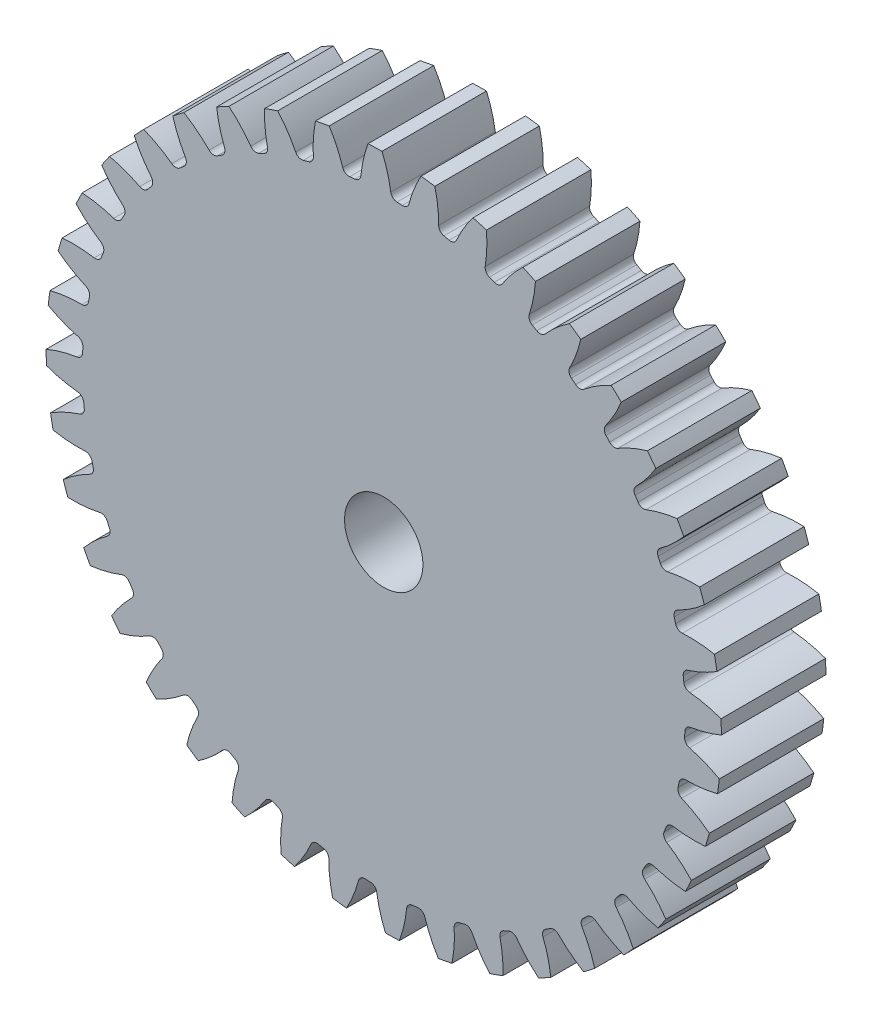
SolidWorks part; units mm, degrees
ref_plane "Front" through (0, 0, 0) normal (0, 0, 1) x (1, 0, 0)
ref_plane "Top" through (0, 0, 0) normal (0, 1, 0) x (1, 0, 0)
ref_plane "Right" through (0, 0, 0) normal (1, 0, 0) x (0, 0, -1)
sketch "Sketch3" plane through (0, 0, 0) normal (0, 0, 1) x (1, 0, 0)
  circle A0 centre (0, 0) radius 20.5154
  dimension "od" = 41.0308
extrude "gearBody" add sketch "Sketch3" along normal blind 6.35
sketch "Sketch2" plane through (0, 0, 0) normal (0, 0, 1) x (1, 0, 0)
  line L0 (0, 0) -> (17.4762, 7.2389) construction
  line L1 (23.4466, -5.3664) -> (0, 0) construction
  line L2 (0, 0) -> (36.3143, 0) construction
  line L3 (19.537, -0.2349) -> (19.4534, -1.8214) construction
  line L5 (19.4952, -1.0281) -> (0, 0) construction
  line L7 (0, 0) -> (18.9161, 0) construction
  arc A0 (18.9123, -0.3796) -> (18.8473, -1.6117) centre (0, 0) ccw construction
  arc A1 (20.5151, 0.1066) -> (20.3901, -2.2639) centre (0, 0) ccw construction
  arc A2 (19.537, -0.2349) -> (19.4534, -1.8214) centre (0, 0) ccw construction
  arc A3 (18.2806, -1.1275) -> (18.2978, -0.8016) centre (0, 0) ccw
  arc A4 (23.4466, -5.3664) -> (18.5763, -1.5357) centre (16.6179, -9.0369) ccw
  arc A5 (23.4466, -5.3664) -> (23.881, 2.8705) centre (0, 0) ccw
  arc A6 (23.881, 2.8705) -> (18.6348, -0.4267) centre (17.4762, 7.2389) cw
  arc A7 (18.2978, -0.8016) -> (18.6348, -0.4267) centre (18.6941, -0.8189) cw
  arc A8 (18.5763, -1.5357) -> (18.2806, -1.1275) centre (18.6765, -1.1519) cw
  point P6 (23.881, 2.8705)
  point P22 (23.4466, -5.3664)
  dimension "baseDia" = 37.8322
  dimension "od" = 41.0308
  dimension "pd" = 39.0769
  dimension "rd" = 36.6307
  dimension "rFillet" = 0.3966
  dimension "pointX" = 23.881
  dimension "pointY" = 2.8705
  dimension "CTT" = 1.5865
  dimension "flankCenterAngle" = 22.5
extrude "toothCut" cut sketch "Sketch2" along normal through all
pattern_circular "CirPattern1" count 40 over 360 about axis through (0, 0, 6.35) along (0, 0, -1) of "toothCut"
ref_axis "toothSpace" through (0, 0, 0) along (0.9986, -0.0527, 0)
ref_axis "Axis2" through (20.339, -2.6845, 0) along (-0.9914, 0.1309, 0)
sketch "hub1Dia" plane through (0, 0, 0) normal (0, 0, -1) x (-1, 0, 0)
  circle A0 centre (0, 0) radius 12.7
  dimension "hub1Dia" = 25.4
sketch "hub2Dia" plane through (0, 0, 6.35) normal (0, 0, 1) x (1, 0, 0)
  circle A0 centre (0, 0) radius 12.7
  dimension "hub2dia" = 25.4
sketch "boreDia" plane through (0, 0, 0) normal (0, 0, 1) x (1, 0, 0)
  circle A0 centre (0, 0) radius 2.3812
  dimension "boreDia" = 4.7625
extrude "bore" cut sketch "boreDia" against normal mid plane 25400
sketch "kwy1sketch" plane through (0, 0, 0) normal (0, 0, 1) x (1, 0, 0)
  line L0 (-6.0395, 0.6368) -> (0, 0) construction
  line L1 (28.9598, 9.717) -> (26.2964, -15.543)
  line L2 (26.2964, -15.543) -> (-5.2785, -12.2138)
  line L3 (28.9598, 9.717) -> (-2.6152, 13.0461)
  line L4 (-5.2785, -12.2138) -> (0, 0)
  line L5 (0, 0) -> (-2.6152, 13.0461)
  line L6 (0, 0) -> (18.2899, -0.9646) construction
  line L7 (27.6281, -2.913) -> (0, 0) construction
  arc A7 (18.2806, -1.1275) -> (18.2978, -0.8016) centre (0, 0) ccw construction
  point P9 (27.6281, -2.913)
  point P13 (-1.0074, 0.1062)
  dimension "kwy1width" = 25.4
  dimension "kwy1depth" = 27.7812
  dimension "kwy1angle" = 3
  dimension "kwy1Depth2" = 31.75
sketch "kwy2sketch" plane through (0, 0, 0) normal (0, 0, 1) x (1, 0, 0)
  line L0 (18.2899, -0.9646) -> (0, 0) construction
  line L1 (0, 0) -> (-3.2623, -2.64) construction
  line L2 (13.6067, 27.3486) -> (29.585, 7.6038)
  line L3 (29.585, 7.6038) -> (4.904, -12.369)
  line L4 (13.6067, 27.3486) -> (-11.0742, 7.3758)
  line L5 (4.904, -12.369) -> (0, 0)
  line L6 (0, 0) -> (-11.0742, 7.3758)
  arc A2 (18.2806, -1.1275) -> (18.2978, -0.8016) centre (0, 0) ccw construction
  point P10 (21.5958, 17.4762)
  dimension "kwy2angle" = 42
  dimension "kwy2Width" = 25.4
  dimension "kwy2depth" = 27.7812
  dimension "kwy2Depth2" = 31.75
sketch "kwy3sketch" plane through (0, 0, 0) normal (0, 0, 1) x (1, 0, 0)
  line L0 (18.2899, -0.9646) -> (0, 0) construction
  line L1 (0, 0) -> (-0.3184, -3.0193) construction
  line L2 (-9.717, 28.9598) -> (15.543, 26.2964)
  line L3 (15.543, 26.2964) -> (12.2138, -5.2785)
  line L4 (-9.717, 28.9598) -> (-13.0461, -2.6152)
  line L5 (12.2138, -5.2785) -> (0, 0)
  line L6 (-13.0461, -2.6152) -> (0, 0)
  point P10 (2.913, 27.6281)
  dimension "kwy3angle" = 87
  dimension "kwy3depth" = 27.7812
  dimension "kwy3width" = 25.4
  dimension "kwy3Depth2" = 31.75
sketch "kwy4sketch" plane through (0, 0, 0) normal (0, 0, 1) x (1, 0, 0)
  line L0 (18.2899, -0.9646) -> (0, 0) construction
  line L1 (0, 0) -> (1.4933, -1.8454) construction
  line L2 (-7.6038, 29.585) -> (-27.3486, 13.6067)
  line L3 (-27.3486, 13.6067) -> (-7.3758, -11.0742)
  line L4 (-7.3758, -11.0742) -> (0, 0)
  line L5 (12.369, 4.904) -> (0, 0)
  line L6 (-7.6038, 29.585) -> (12.369, 4.904)
  point P15 (-17.4762, 21.5958)
  dimension "kwy4angle" = 132
  dimension "kwy4depth" = 27.7812
  dimension "kwy4width" = 25.4
  dimension "kwy4Depth2" = 31.75
sketch "kwy5sketch" plane through (0, 0, 0) normal (0, 0, 1) x (1, 0, 0)
  line L0 (18.2899, -0.9646) -> (0, 0) construction
  line L1 (0, 0) -> (2.0276, -0.2138) construction
  line L2 (-26.2964, 15.543) -> (-28.9598, -9.717)
  line L3 (-28.9598, -9.717) -> (2.6152, -13.0461)
  line L4 (-26.2964, 15.543) -> (5.2785, 12.2138)
  line L5 (2.6152, -13.0461) -> (0, 0)
  line L6 (5.2785, 12.2138) -> (0, 0)
  point P10 (-27.6281, 2.913)
  dimension "kwy5width" = 25.4
  dimension "kwy5depth" = 27.7812
  dimension "kwy5angle" = 177
  dimension "kwy5Depth2" = 31.75
sketch "kwy6sketch" plane through (0, 0, 0) normal (0, 0, 1) x (1, 0, 0)
  line L0 (18.2899, -0.9646) -> (0, 0) construction
  line L1 (0, 0) -> (1.5836, 1.2815) construction
  line L2 (-29.585, -7.6038) -> (-13.6067, -27.3486)
  line L3 (-13.6067, -27.3486) -> (11.0742, -7.3758)
  line L4 (-29.585, -7.6038) -> (-4.904, 12.369)
  line L5 (11.0742, -7.3758) -> (0, 0)
  line L6 (-4.904, 12.369) -> (0, 0)
  point P10 (-21.5958, -17.4762)
  dimension "kwy6angle" = 222
  dimension "kwy6width" = 25.4
  dimension "kwy6depth" = 27.7812
  dimension "kwy6Depth2" = 31.75
sketch "kwy7sketch" plane through (0, 0, 0) normal (0, 0, 1) x (1, 0, 0)
  line L0 (18.2899, -0.9646) -> (0, 0) construction
  line L1 (0, 0) -> (0.2393, 2.2697) construction
  line L2 (-15.543, -26.2964) -> (9.717, -28.9598)
  line L3 (-15.543, -26.2964) -> (-12.2138, 5.2785)
  line L4 (9.717, -28.9598) -> (13.0461, 2.6152)
  line L5 (-12.2138, 5.2785) -> (0, 0)
  line L6 (13.0461, 2.6152) -> (0, 0)
  point P10 (-2.913, -27.6281)
  dimension "kwy7angle" = 87
  dimension "kwy7width" = 25.4
  dimension "kwy7depth" = 27.7812
  dimension "kwy7angle1" = 267
  dimension "kwy7Depth2" = 31.75
sketch "kwy8sketch" plane through (0, 0, 0) normal (0, 0, 1) x (1, 0, 0)
  line L0 (18.2899, -0.9646) -> (0, 0) construction
  line L1 (0, 0) -> (-1.2755, 1.5762) construction
  line L2 (7.6038, -29.585) -> (27.3486, -13.6067)
  line L3 (27.3486, -13.6067) -> (7.3758, 11.0742)
  line L4 (7.6038, -29.585) -> (-12.369, -4.904)
  line L5 (7.3758, 11.0742) -> (0, 0)
  line L6 (-12.369, -4.904) -> (0, 0)
  point P10 (17.4762, -21.5958)
  dimension "kwy8angle" = 312
  dimension "kwy8width" = 25.4
  dimension "kwy8depth" = 27.7812
  dimension "kwy8Depth2" = 31.75
sketch "centerLine" plane through (0, 0, 0) normal (0, 1, 0) x (1, 0, 0)
  line L0 (0, 36.4807) -> (0, -59.6309) construction
ref_plane "CB1plane" through (0, 0, 0) normal (0, 0, -1) x (-1, 0, 0)
sketch "CB1diameter" plane through (0, 0, 0) normal (0, 0, -1) x (-1, 0, 0)
  circle A0 centre (0, 0) radius 12.7
  dimension "CB1diameter" = 25.4
ref_plane "CB2plane" through (0, 0, 6.35) normal (0, 0, 1) x (1, 0, 0)
sketch "CB2diameter" plane through (0, 0, 6.35) normal (0, 0, 1) x (1, 0, 0)
  circle A0 centre (0, 0) radius 12.7
  dimension "CB2diameter" = 25.4
ref_axis "Axis1" through (0, 0, 50) along (0, 0, -1)
sketch "Sketch4" plane through (0, 0, 6.35) normal (0, 0, 1) x (1, 0, 0)
  circle A0 centre (0, 0) radius 19.5326
  dimension "D1" = 39.0652
